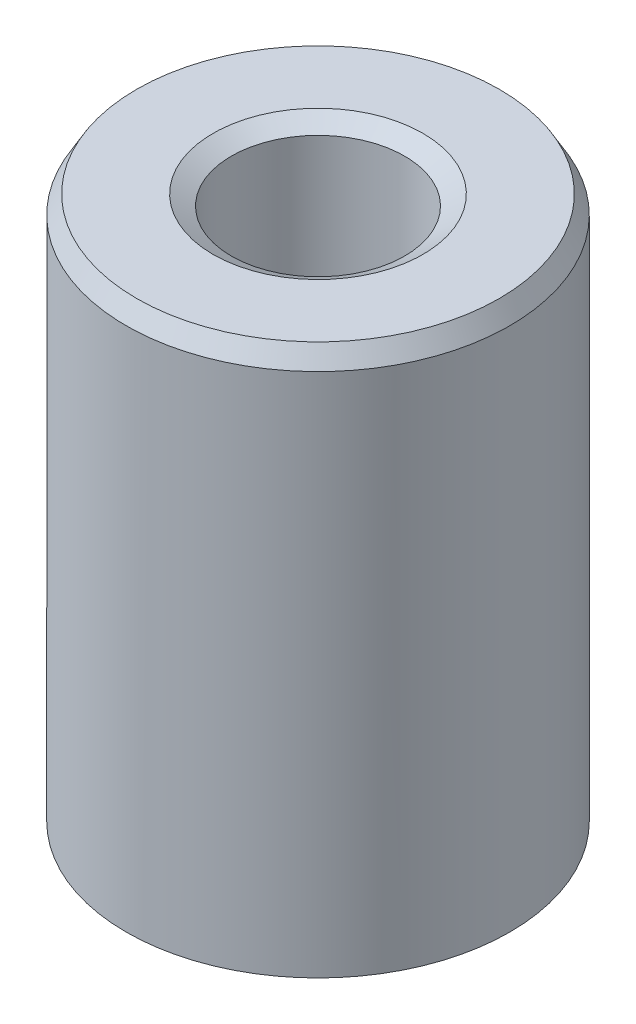
SolidWorks part; units mm, degrees
ref_plane "Front Plane" through (0, 0, 0) normal (0, 0, 1) x (1, 0, 0)
ref_plane "Top Plane" through (0, 0, 0) normal (0, 1, 0) x (1, 0, 0)
ref_plane "Right Plane" through (0, 0, 0) normal (1, 0, 0) x (0, 0, -1)
sketch "Sketch1" plane through (0, 0, 0) normal (0, 1, 0) x (1, 0, 0)
  circle A0 centre (0, 0) radius 17.5
  dimension "SLEEVE_OD" = 35
extrude "Boss-Extrude1" add sketch "Sketch1" along normal blind 50.5358
sketch "Sketch2" plane through (0, 0, 0) normal (0, 1, 0) x (1, 0, 0)
  circle A0 centre (0, 0) radius 7.904
  dimension "BORE_D" = 15.808
extrude "Cut-Extrude1" cut sketch "Sketch2" along normal through all
chamfer "Chamfer1" distance 1.6675 angle 30 4 edges at (0, 50.5358, 7.904) (0, 0, 7.904) (0, 0, 17.5) (0, 50.5358, 17.5) first distance on face at (0, 50.5358, 7.904) first distance on face at (0, 0, 7.904) first distance on face at (0, 50.5358, 17.5)
